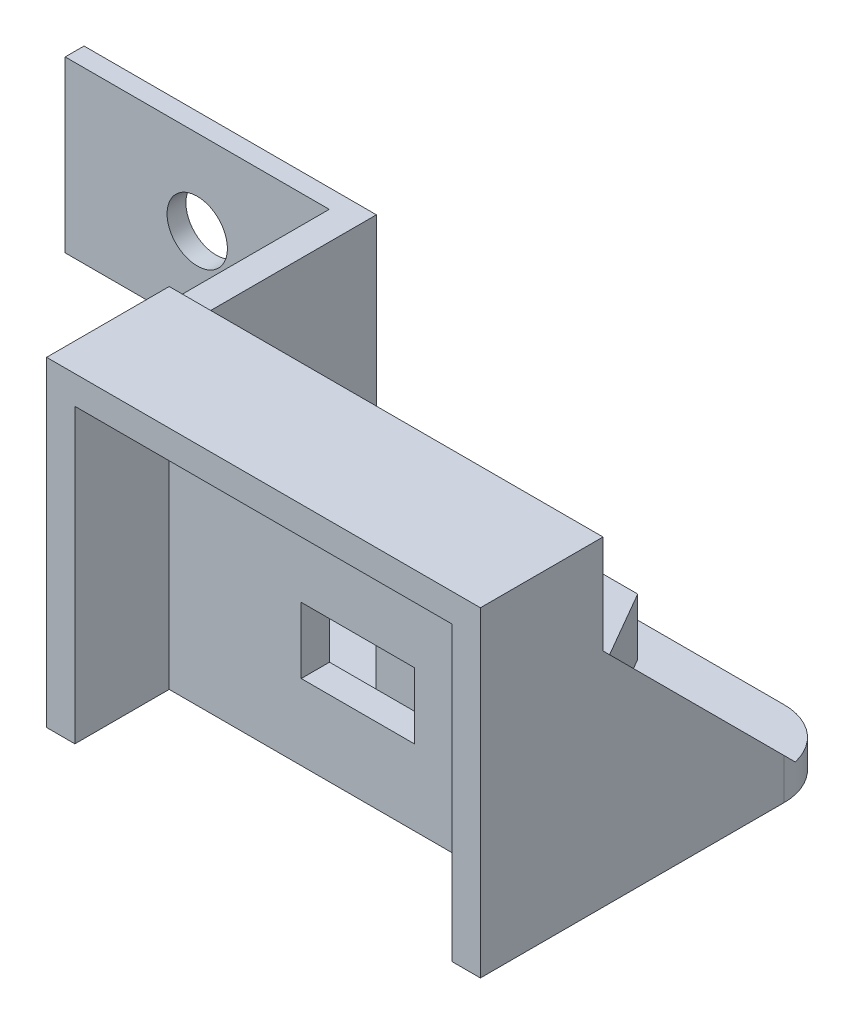
SolidWorks part; units mm, degrees
ref_plane "前视基准面" through (0, 0, 0) normal (0, 0, 1) x (1, 0, 0)
ref_plane "上视基准面" through (0, 0, 0) normal (0, 1, 0) x (1, 0, 0)
ref_plane "右视基准面" through (0, 0, 0) normal (1, 0, 0) x (0, 0, -1)
sketch "草图1" plane through (0, 0, 0) normal (0, 0, 1) x (1, 0, 0)
  line L1 (-11.5, 8.5) -> (11.5, 8.5)
  line L2 (-11.5, 8.5) -> (-11.5, -8.5)
  line L3 (-11.5, -8.5) -> (11.5, -8.5)
  line L4 (11.5, 8.5) -> (11.5, -8.5)
  line L5 (-11.5, 8.5) -> (11.5, -8.5) construction
  line L6 (-11.5, -8.5) -> (11.5, 8.5) construction
  point P0 (0, 0)
  dimension "D1" = 23
  dimension "D2" = 17
extrude "凸台-拉伸1" add sketch "草图1" along normal blind 6.5
sketch "草图2" plane through (0, 0, 6.5) normal (0, 0, 1) x (1, 0, 0)
  line L0 (0, -9.35) -> (0, 9.35) construction
  line L1 (-10, 7) -> (10, 7)
  line L2 (-10, 7) -> (-10, -8.5)
  line L3 (-10, -8.5) -> (10, -8.5)
  line L4 (10, 7) -> (10, -8.5)
  line L5 (-10, 7) -> (10, -8.5) construction
  line L6 (-10, -8.5) -> (10, 7) construction
  line L7 (-11.5, -8.5) -> (11.5, -8.5) construction
  line L8 (11.5, 8.5) -> (-11.5, 8.5) construction
  line L9 (-11.5, 8.5) -> (-11.5, -8.5) construction
  line L10 (11.5, -8.5) -> (11.5, 8.5) construction
  point P0 (0, -0.75)
  dimension "D1" = 1.5
  dimension "D2" = 1.5
  dimension "D3" = 1.5
extrude "切除-拉伸1" cut sketch "草图2" against normal blind 5
sketch "草图3" plane through (0, 0, 0) normal (0, 0, -1) x (-1, 0, 0)
  line L0 (-11.5, -8.5) -> (-11.5, 8.5) construction
  line L1 (-11.5, -7) -> (11.5, -7)
  line L2 (-11.5, -7) -> (-11.5, -8.5)
  line L3 (-11.5, -8.5) -> (11.5, -8.5)
  line L4 (11.5, -7) -> (11.5, -8.5)
  dimension "D1" = 1.5
extrude "凸台-拉伸2" add sketch "草图3" along normal blind 12.6
sketch "草图4" plane through (0, -7, 0) normal (0, 1, 0) x (1, 0, 0)
  line L0 (5.0807, 6.4) -> (2.5403, 10.8)
  line L1 (3.3486, 6.4) -> (1.6743, 9.3)
  line L2 (1.6743, 9.3) -> (-1.6743, 9.3)
  line L3 (-1.6743, 9.3) -> (-3.3486, 6.4)
  line L4 (-3.3486, 6.4) -> (-1.6743, 3.5)
  line L5 (-1.6743, 3.5) -> (1.6743, 3.5)
  line L6 (1.6743, 3.5) -> (3.3486, 6.4)
  line L7 (2.5403, 10.8) -> (-2.5403, 10.8)
  line L8 (-2.5403, 10.8) -> (-5.0807, 6.4)
  line L9 (-5.0807, 6.4) -> (-2.5403, 2)
  line L10 (-2.5403, 2) -> (2.5403, 2)
  line L11 (2.5403, 2) -> (5.0807, 6.4)
  line L12 (0, -9.35) -> (0, 9.35) construction
  line L13 (-11.5, 0) -> (11.5, 0) construction
  line L14 (-11.5, 12.6) -> (11.5, 12.6) construction
  circle A0 centre (0, 6.4) radius 2.9 construction
  dimension "D1" = 5.8
  dimension "D3" = 2
  dimension "D4" = 1.8
  dimension "D2" = 1.5
extrude "凸台-拉伸3" add sketch "草图4" along normal blind 3
hole_wizard "M3 间隙孔1" positions "草图8" profile "草图9" hole size "M3" standard "ISO" end condition up to next
sketch "草图8" plane through (0, -7, 0) normal (0, 1, 0) x (1, 0, 0)
  point P0 (0, 6.4)
sketch "草图9" plane through (0, -7, -6.4) normal (1, 0, 0) x (0, 0, 1)
  line L0 (0, 0) -> (0, 1.5)
  line L1 (0, 1.5) -> (1.6, 1.5)
  line L2 (1.6, 1.5) -> (1.6, 0)
  line L5 (1.6, 0) -> (0, 0)
  line L11 (0, -6.35) -> (0, 107.95) construction
  dimension "通孔孔直径" = 3.2
  dimension "通孔孔深度" = 1.5
ref_plane "基准面4" through (0, -3.5, -3.5) normal (0, -0.7071, -0.7071) x (-1, 0, 0)
sketch "草图7" plane through (0, -3.5, -3.5) normal (0, -0.7071, -0.7071) x (-1, 0, 0)
  line L0 (-11.5, -10.6066) -> (-11.5, 2.8991) construction
  line L1 (-10, -4.9497) -> (-11.5, -4.9497)
  line L2 (-10, -4.9497) -> (-10, 2.3101)
  line L3 (-10, 2.3101) -> (-11.5, 2.3101)
  line L4 (-11.5, -4.9497) -> (-11.5, 2.3101)
  line L5 (11.5, -4.9497) -> (-11.5, -4.9497) construction
  dimension "D1" = 1.5
extrude "凸台-拉伸6" add sketch "草图7" along normal up to surface and the other way up to surface up to face at (0, -7, -6.3) other way up to face at (0, 0.75, 0)
fillet "圆角1" radius 3 2 edges at (-11.5, -7.75, -12.6) (11.5, -7.75, -12.6)
sketch "草图10" plane through (0, 0, 0) normal (0, 0, -1) x (-1, 0, 0)
  line L0 (11.5, 8.5) -> (11.5, -7) construction
  line L1 (11.5, 7.8) -> (10, 7.8)
  line L2 (11.5, 7.8) -> (11.5, -1.2)
  line L3 (11.5, -1.2) -> (10, -1.2)
  line L4 (10, 7.8) -> (10, -1.2)
  line L5 (25.5, -1.2) -> (11.5, -1.2) construction
  dimension "D1" = 1.5
  dimension "D2" = 9
extrude "凸台-拉伸7" add sketch "草图10" along normal up to surface (9.4863 mm away) up to face at (0, -0.375, 6.5)
sketch "草图11" plane through (-11.5, 0, 0) normal (-1, 0, 0) x (0, 0, 1)
  line L0 (-9.4863, -1.2) -> (0, -1.2) construction
  line L1 (-9.4863, 7.8) -> (-8.4863, 7.8)
  line L2 (-9.4863, 7.8) -> (-9.4863, -1.2)
  line L3 (-9.4863, -1.2) -> (-8.4863, -1.2)
  line L4 (-8.4863, 7.8) -> (-8.4863, -1.2)
  dimension "D1" = 1
extrude "凸台-拉伸8" add sketch "草图11" along normal up to surface (14 mm away) up to face at (0, -8.5, -4.8)
hole_wizard "M3 间隙孔2" positions "草图12" profile "草图13" hole size "M3" standard "ISO" end condition up to next
sketch "草图12" plane through (0, 0, -8.4863) normal (0, 0, 1) x (1, 0, 0)
  point P0 (-18.5, 3.3)
sketch "草图13" plane through (-18.5, 3.3, -8.4863) normal (1, 0, 0) x (0, -1, 0)
  line L0 (0, 0) -> (0, 1)
  line L1 (0, 1) -> (1.6, 1)
  line L2 (1.6, 1) -> (1.6, 0)
  line L5 (1.6, 0) -> (0, 0)
  line L11 (0, -6.35) -> (0, 107.95) construction
  dimension "通孔孔直径" = 3.2
  dimension "通孔孔深度" = 1
sketch "草图14" plane through (0, 0, 0) normal (0, 0, -1) x (-1, 0, 0)
  line L1 (3, -1) -> (-3, -1)
  line L2 (3, -1) -> (3, -4.5)
  line L3 (3, -4.5) -> (-3, -4.5)
  line L4 (-3, -1) -> (-3, -4.5)
extrude "切除-拉伸2" cut sketch "草图14" against normal up to next
